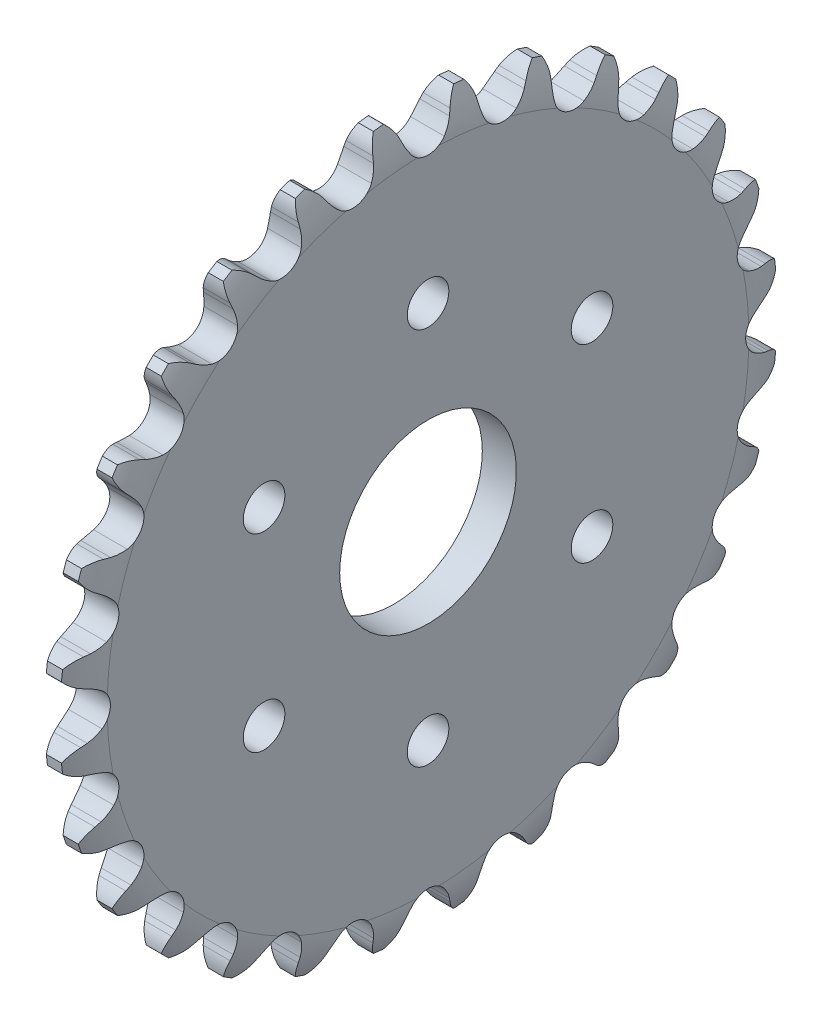
SolidWorks part; units mm, degrees
material "6061-T6 (SS)"
ref_plane "Plane1" through (0, 0, 0) normal (0, 0, 1) x (1, 0, 0)
ref_plane "Plane2" through (0, 0, 0) normal (0, 1, 0) x (1, 0, 0)
ref_plane "Plane3" through (0, 0, 0) normal (1, 0, 0) x (0, 0, -1)
sketch "Clipboard" plane through (0, 0, 0) normal (0, 1, 0) x (1, 0, 0)
  line L0 (0, 0) -> (8.4101, -4.4717)
  line L1 (-15, 0) -> (100, 0) construction
  line L2 (0, 0) -> (-0.7911, 0.8941)
  line L3 (0, 0) -> (-4.4605, 1.7048)
  line L4 (0, 0) -> (4.2163, 2.2418)
  line L5 (0, 0) -> (-47.5972, -17.7524)
  line L6 (0, 0) -> (-3.555, -2.3986)
  line L7 (-0.7911, 0.8941) -> (43.6397, 25.5224)
  line L8 (-76.2, 38.1) -> (-51.7144, 38.1)
  line L9 (-73.2057, 38.5609) -> (-73.0533, 38.5634)
  line L10 (-73.0533, 76.1892) -> (-62.9187, 76.1892)
  circle A0 centre (0, 0) radius 2.54
  circle A1 centre (0, 0) radius 37.1249
  circle A2 centre (0, 0) radius 38.1
  dimension "Dr" = 5.08
  dimension "MHD" = 74.2497
  dimension "Hub_dia" = 76.2
  dimension "Num_teeth" = 28
  dimension "Pitch" = 9.525
  dimension "Width" = 4.7752
  dimension "Chamfer_wid" = 1.1938
  dimension "Chamfer_dep" = 4.7752
  dimension "Overall_len" = 50.8
  dimension "Show_teeth" = 28
  dimension "Thickness" = 4.2885
  dimension "OAL" = 50.8001
  dimension "T_dim" = 24.4856
  dimension "Width_const" = 0.1524
  dimension "Width_factor" = 0.93
  dimension "Num_strands" = 1
  dimension "Transv_pitch" = 10.1346
sketch "BasProSke" plane through (0, 0, 0) normal (0, 1, 0) x (1, 0, 0)
  line L0 (-10, 0) -> (60, 0) construction
  line L1 (0, 0) -> (0, 40.3507)
  line L2 (0, 0) -> (4.2885, 0)
  line L3 (4.2885, 0) -> (4.2885, 40.3507)
  line L4 (3.0947, 45.1259) -> (1.1938, 45.1259)
  arc A0 (0, 40.3507) -> (1.1938, 45.1259) centre (10.1473, 40.3507) cw
  arc A1 (4.2885, 40.3507) -> (3.0947, 45.1259) centre (-5.8588, 40.3507) ccw
  dimension "D1" = 10.1473
  dimension "G1" = 1.1938
  dimension "G2" = 1.1938
  dimension "H2" = 4.7752
  dimension "Diameter" = 90.2517
  dimension "H1" = 4.7752
  dimension "Thickness" = 4.2885
revolve "Base-Revolve" add sketch "BasProSke" angle 360 about L0
sketch "GrvSke" plane through (0, 0, 0) normal (0, 1, 0) x (1, 0, 0)
  line L0 (4.2885, 40.3507) -> (4.2885, 37.1249)
  line L1 (4.2885, 37.1249) -> (10.1346, 37.1249)
  line L2 (10.1346, 37.1249) -> (10.1346, 40.3507)
  line L3 (3.0947, 45.1259) -> (11.3284, 45.1259)
  line L4 (7.2116, 0) -> (7.2116, 52.07) construction
  line L5 (-10, 0) -> (60, 0) construction
  line L6 (0, 0) -> (35.56, 0) construction
  arc A0 (10.1346, 40.3507) -> (11.3284, 45.1259) centre (20.2819, 40.3507) cw
  arc A1 (4.2885, 40.3507) -> (3.0947, 45.1259) centre (-5.8588, 40.3507) ccw
  dimension "Diameter" = 90.2517
  dimension "H1" = 4.7752
  dimension "Grv_diam" = 74.2497
  dimension "Grv_width" = 5.8461
  dimension "Offset" = 7.2116
  dimension "G1" = 1.1938
revolve "Groove" [suppressed] cut sketch "GrvSke" angle 360 about L6
pattern_linear "Grooves" [suppressed]
sketch "TooCutSke" plane through (0, 0, 0) normal (1, 0, 0) x (0, 0, -1)
  line L0 (2.9673, 42.5893) -> (3.2148, 43.2294)
  line L1 (0, 0) -> (0, 107) construction
  line L2 (0, 42.5358) -> (-10, 42.5358) construction
  line L3 (-2.9673, 42.5893) -> (-3.2148, 43.2294)
  arc A0 (2.0652, 40.9715) -> (2.9673, 42.5893) centre (-3.2395, 44.9897) ccw
  arc A1 (2.0652, 40.9715) -> (-2.0652, 40.9715) centre (0, 42.5358) cw
  arc A2 (3.2148, 43.2294) -> (7.0673, 45.87) centre (7.0673, 41.7395) cw
  arc A3 (-2.0652, 40.9715) -> (-2.9673, 42.5893) centre (3.2395, 44.9897) cw
  arc A4 (-3.2148, 43.2294) -> (-7.0673, 45.87) centre (-7.0673, 41.7395) ccw
  arc A5 (7.0673, 45.87) -> (-7.0673, 45.87) centre (0, 0) ccw
  dimension "R" = 2.5908
  dimension "E" = 6.6548
  dimension "F" = 4.1305
  dimension "Pitch_radius" = 42.5358
  dimension "W" = 7.0673
  dimension "V" = 0.7963
  dimension "A" = 37.143
  dimension "B" = 16
extrude "ToothCut" cut sketch "TooCutSke" along normal through all
pattern_circular "TeethCuts" count 28 every 12.857 about axis through (-10, 0, 0) along (1, 0, 0) of "ToothCut"
sketch "HubNeaOneSke" plane through (0, 0, 0) normal (-1, 0, 0) x (0, 0, 1)
  circle A0 centre (0, 0) radius 37.1249
  dimension "Diameter" = 74.2497
extrude "HubNearOne" [suppressed] add sketch "HubNeaOneSke" along normal blind 46.5115
sketch "HubNeaBotSke" plane through (0, 0, 0) normal (-1, 0, 0) x (0, 0, 1)
  circle A0 centre (0, 0) radius 37.1249
  dimension "Diameter" = 74.2497
extrude "HubNearBoth" [suppressed] add sketch "HubNeaBotSke" along normal blind 23.2558
ref_plane "FarPln" through (4.2885, 0, 0) normal (1, 0, 0) x (0, 0, -1)
sketch "HubFarSke" plane through (4.2885, 0, 0) normal (1, 0, 0) x (0, 0, -1)
  circle A0 centre (0, 0) radius 37.1249
  dimension "Diameter" = 74.2497
extrude "HubFar" [suppressed] add sketch "HubFarSke" along normal blind 23.2558
sketch "BorSke" plane through (0, 0, 0) normal (1, 0, 0) x (0, 0, -1)
  circle A0 centre (0, 0) radius 11.1125
  dimension "Diameter" = 22.225
extrude "Bore" cut sketch "BorSke" along normal mid plane 101.6001
sketch "KeySke" plane through (0, 0, 0) normal (1, 0, 0) x (0, 0, -1)
  line L0 (-2.3813, 0) -> (-2.3813, 13.3731)
  line L1 (-2.3813, 13.3731) -> (2.3813, 13.3731)
  line L2 (2.3813, 13.3731) -> (2.3813, 0)
  line L3 (0, 0) -> (0, 34) construction
  line L4 (-2.3813, 0) -> (2.3813, 0)
  dimension "Offset" = 13.3731
  dimension "Width" = 4.7625
extrude "Keyway" [suppressed] cut sketch "KeySke" along normal mid plane 101.6001
pattern_circular "Keyway2" [suppressed] count 2 every 90 about axis through (-10, 0, 0) along (1, 0, 0)
sketch "Sketch1" plane through (4.2885, 0, 0) normal (1, 0, 0) x (0, 0, -1)
  arc A0 (-2.6122, 23.6688) -> (2.6122, 23.6688) centre (0, 0) ccw
  circle A1 centre (0, 23.8125) radius 2.6162
  dimension "D1" = 47.625
  dimension "D2" = 5.2324
extrude "Extrude1" cut sketch "Sketch1" against normal through all contours A1 region at (4.2885, 23.8125, 0)
pattern_circular "CirPattern1" count 6 over 360 about axis through (4.2885, 0, 0) along (1, 0, 0) of "Extrude1"
equation "\"Num_teeth@Clipboard\" = int( \"Num_teeth@Clipboard\" )"
equation "\"Num_teeth@Clipboard\" = ((sgn( \"Num_teeth@Clipboard\" - 5.0)+1)*( \"Num_teeth@Clipboard\" - 5.0))/2 +5.0"
equation "\"Num_teeth@Clipboard\" = ((sgn( \"Num_teeth@Clipboard\" - 200.0)-1)*( \"Num_teeth@Clipboard\" - 200.0))/-2 +200.0"
equation "\"MHD@Clipboard\" = \"Pitch@Clipboard\" * (1.0 / tan(3.14159265 / \"Num_teeth@Clipboard\" ) - 1.0) - 0.03"
equation "\"Thickness@Clipboard\"  = \"Width@Clipboard\" * \"Width_factor@Clipboard\" - \"Width_const@Clipboard\" + (\"Num_strands@Clipboard\" - 1) * \"Transv_pitch@Clipboard\""
equation "\"OAL@Clipboard\" = \"Thickness@Clipboard\""
equation "\"MHD@Clipboard\" = ((sgn( \"MHD@Clipboard\" - \"Hub_dia@Clipboard\" )-1)*( \"MHD@Clipboard\" - \"Hub_dia@Clipboard\" ))/-2+ \"Hub_dia@Clipboard\""
equation "\"OAL@Clipboard\" = ((sgn( \"OAL@Clipboard\" - \"Overall_len@Clipboard\" )+1)*( \"OAL@Clipboard\" - \"Overall_len@Clipboard\" ))/2 + \"Overall_len@Clipboard\" + 0.000002"
equation "\"Num_teeth@TeethCuts\" = int( \"Show_teeth@Clipboard\" ) + 1"
equation "\"Num_teeth@TeethCuts\" = ((sgn( \"Num_teeth@TeethCuts\" - \"Num_teeth@Clipboard\" )-1)*( \"Num_teeth@TeethCuts\" - \"Num_teeth@Clipboard\" ))/-2+ \"Num_teeth@Clipboard\""
equation "\"Num_teeth@TeethCuts\" = ((sgn( \"Num_teeth@TeethCuts\" - 2.0)+1)*( \"Num_teeth@TeethCuts\" - 2.0))/2 +2.0"
equation "\"Angle@TeethCuts\" = 360.0 / \"Num_teeth@Clipboard\""
equation "\"Pitch_radius@TooCutSke\" = ( \"Pitch@Clipboard\" / 2.0) / sin(3.14159265 / \"Num_teeth@Clipboard\" )  'ma"
equation "\"R@TooCutSke\"  = \"Dr@Clipboard\" * 0.5025 + 0.0015"
equation "\"A@TooCutSke\" = 35.0 + (60.0 / \"Num_teeth@Clipboard\")"
equation "\"E@TooCutSke\"  = \"Dr@Clipboard\" * 1.3025 + 0.0015"
equation "\"B@TooCutSke\"  = 18.0 - (56.0 / \"Num_teeth@Clipboard\" )"
equation "\"W@TooCutSke\" = 1.4 * \"Dr@Clipboard\" * cos(3.14159265 / \"Num_teeth@Clipboard\" )"
equation "\"V@TooCutSke\" = 1.4 * \"Dr@Clipboard\" * sin(3.14159265 / \"Num_teeth@Clipboard\" )"
equation "\"Diameter@BasProSke\" = 2.0 * ( (0.3 * \"Pitch@Clipboard\" ) +  \"Pitch@Clipboard\" / 2.0 / tan(3.14159265 / \"Num_teeth@Clipboard\" ))"
equation "\"Thickness@BasProSke\"  = \"Thickness@Clipboard\""
equation "\"G1@BasProSke\" =  \"Chamfer_wid@Clipboard\""
equation "\"G2@BasProSke\" =  \"Chamfer_wid@Clipboard\""
equation "\"H1@BasProSke\" =  \"Chamfer_dep@Clipboard\""
equation "\"H2@BasProSke\" =  \"Chamfer_dep@Clipboard\""
equation "\"Diameter@GrvSke\" = \"Diameter@BasProSke\""
equation "\"G1@GrvSke\" = \"Chamfer_wid@Clipboard\""
equation "\"H1@GrvSke\" = \"Chamfer_dep@Clipboard\""
equation "\"Grv_diam@GrvSke\" =  \"Pitch@Clipboard\" * (1.0 / tan(3.14159265 / \"Num_teeth@Clipboard\" ) - 1.0) - 0.03"
equation "\"Grv_width@GrvSke\" =  \"Transv_pitch@Clipboard\" - ( \"Width@Clipboard\" * \"Width_factor@Clipboard\" - \"Width_const@Clipboard\" )"
equation "\"Offset@GrvSke\" = \"Grv_width@GrvSke\" / 2.0 + ( \"Width@Clipboard\" * \"Width_factor@Clipboard\" - \"Width_const@Clipboard\" )"
equation "\"Offset@Grooves\" = \"Transv_pitch@Clipboard\""
equation "\"Num_grvs@Grooves\" = \"Num_strands@Clipboard\""
equation "\"Num_grvs@Grooves\" = \"Num_grvs@Grooves\" - 1 * sgn( \"Num_grvs@Grooves\" -1)"
equation "\"Diameter@HubNeaOneSke\" = \"MHD@Clipboard\""
equation "\"Length@HubNearOne\" = \"OAL@Clipboard\" - \"Thickness@BasProSke\""
equation "\"Diameter@HubNeaBotSke\" = \"MHD@Clipboard\""
equation "\"Length@HubNearBoth\" = ( \"OAL@Clipboard\" - \"Thickness@BasProSke\" ) / 2.0"
equation "\"Thickness@FarPln\" = \"Thickness@BasProSke\""
equation "\"Diameter@HubFarSke\" = \"MHD@Clipboard\""
equation "\"Length@HubFar\" = ( \"OAL@Clipboard\" - \"Thickness@BasProSke\" ) / 2.0"
equation "\"D1@Bore\" = \"OAL@Clipboard\" * 2.0"
equation "\"D1@Keyway\" = \"OAL@Clipboard\" * 2.0"
equation "\"Offset@KeySke\" = \"T_dim@Clipboard\" - \"Diameter@BorSke\" / 2.0"
